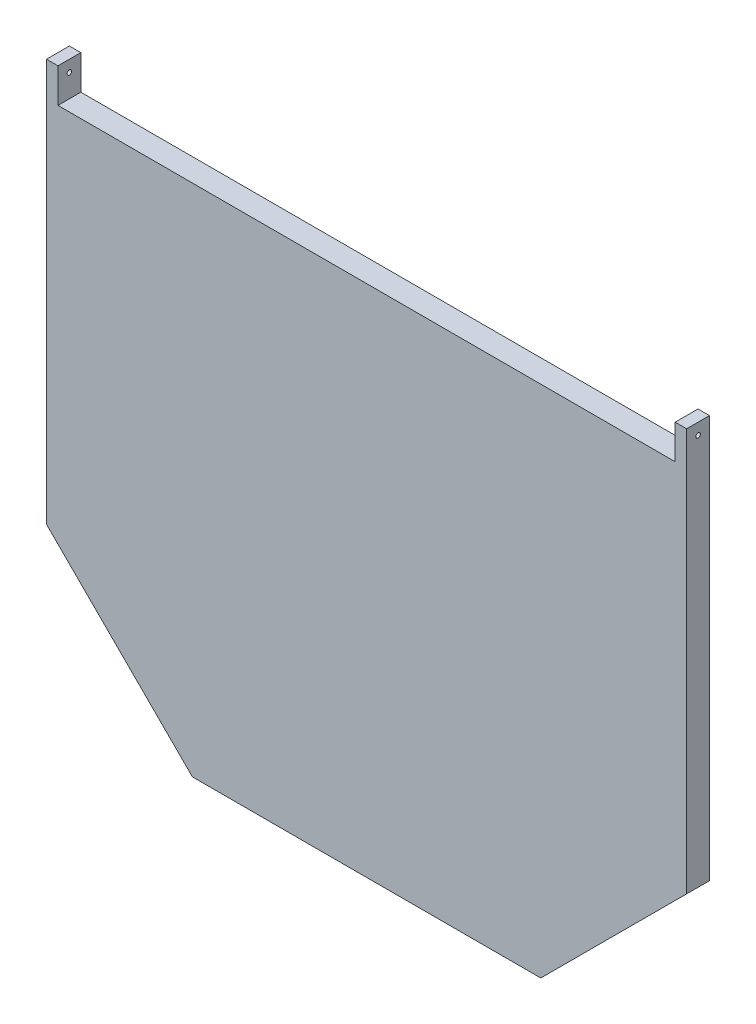
SolidWorks part; units mm, degrees
ref_plane "Front" through (0, 0, 0) normal (0, 0, 1) x (1, 0, 0)
ref_plane "Top" through (0, 0, 0) normal (0, 1, 0) x (1, 0, 0)
ref_plane "Right" through (0, 0, 0) normal (1, 0, 0) x (0, 0, -1)
sketch "Sketch1" plane through (0, 0, 0) normal (0, 0, 1) x (1, 0, 0)
  line L8 (0, 0) -> (355.6, 0)
  line L10 (0, 0) -> (0, -223.774)
  line L11 (0, -223.774) -> (81.026, -304.7518)
  line L12 (81.026, -304.7518) -> (274.574, -304.7518)
  line L13 (274.574, -304.7518) -> (355.6, -223.774)
  line L14 (355.6, -223.774) -> (355.6, 0)
  dimension "D1" = 223.774
  dimension "D2" = 355.6
  dimension "D3" = 114.554
  dimension "D4" = 193.548
extrude "Boss-Extrude1" add sketch "Sketch1" along normal blind 12.7
sketch "Sketch2" plane through (0, 0, 12.7) normal (0, 0, 1) x (1, 0, 0)
  line L0 (355.6, 0) -> (0, 0) construction
  line L1 (6.35, -19.05) -> (349.25, -19.05)
  line L2 (6.35, -19.05) -> (6.35, 0)
  line L3 (6.35, 0) -> (349.25, 0)
  line L4 (349.25, -19.05) -> (349.25, 0)
  dimension "D1" = 19.05
extrude "Cut-Extrude1" cut sketch "Sketch2" against normal through all
sketch "Sketch3" plane through (0, 0, 0) normal (-1, 0, 0) x (0, 0, 1)
  line L0 (12.7, 0) -> (12.7, -223.774) construction
  line L1 (12.7, 0) -> (0, 0) construction
  circle A0 centre (6.35, -6.35) radius 1.27
  dimension "D1" = 2.54
  dimension "D2" = 6.35
  dimension "D3" = 6.35
extrude "Cut-Extrude2" cut sketch "Sketch3" against normal through all
